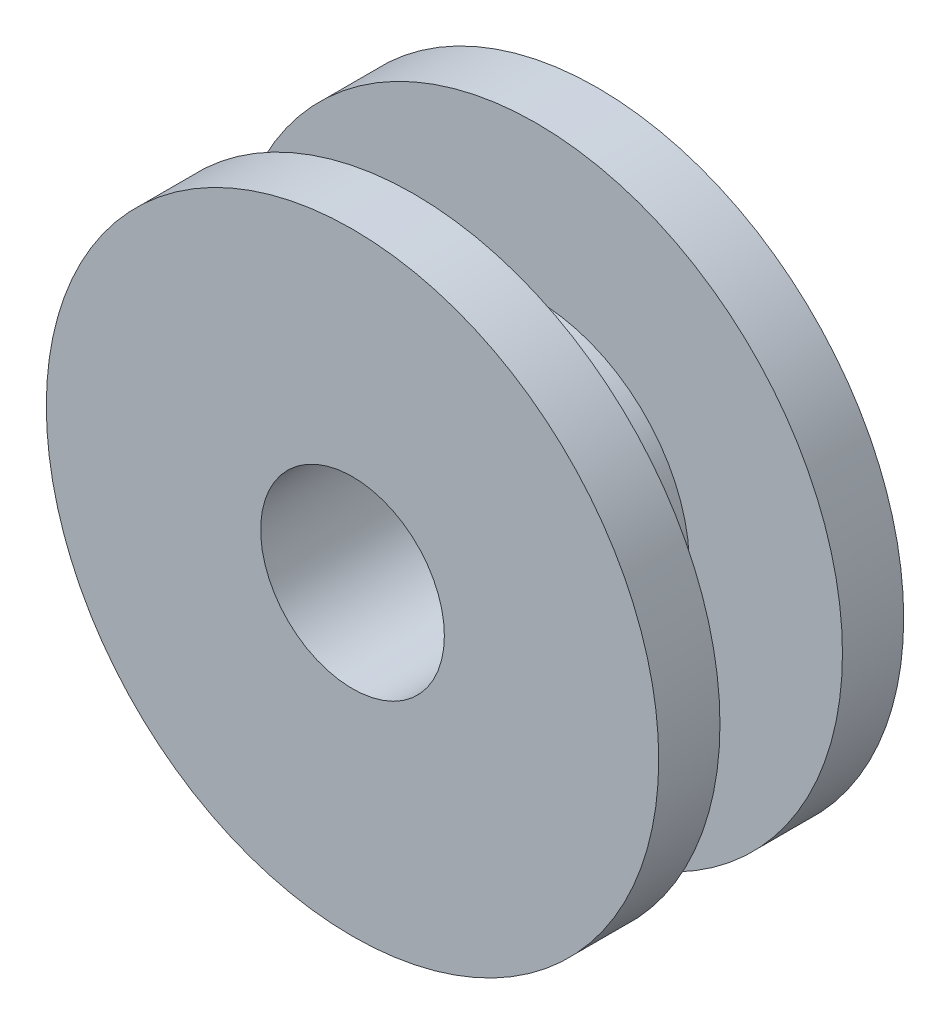
SolidWorks part; units mm, degrees
ref_plane "Front Plane" through (0, 0, 0) normal (0, 0, 1) x (1, 0, 0)
ref_plane "Top Plane" through (0, 0, 0) normal (0, 1, 0) x (1, 0, 0)
ref_plane "Right Plane" through (0, 0, 0) normal (1, 0, 0) x (0, 0, -1)
sketch "Sketch1" plane through (0, 0, 0) normal (0, 0, 1) x (1, 0, 0)
  line L0 (0, 0) -> (0, -2.3) construction
  line L3 (-5, -8) -> (5, -8)
  line L5 (0, -2.3) -> (-3.5, -2.3) construction
  line L6 (-5, 0) -> (-5, -8)
  line L7 (-3.5, -2.3) -> (3.5, -2.3)
  line L8 (-3.5, -2.3) -> (-3.5, -6.3)
  line L9 (-3.5, -6.3) -> (3.5, -6.3)
  line L10 (3.5, -2.3) -> (3.5, -6.3)
  line L11 (5, 0) -> (5, -8)
  circle A1 centre (0, 0) radius 3
  arc A2 (5, 0) -> (-5, 0) centre (0, 0) ccw
  dimension "D1" = 8
  dimension "D4" = 6
  dimension "D5" = 3.5
  dimension "D6" = 7
  dimension "D7" = 4
  dimension "D8" = 2.3
extrude "Boss-Extrude1" add sketch "Sketch1" along normal blind 7 contours L3 A1 L7 L10 L9 L8 region at (-4.836, -4, 0)
sketch "Sketch2" plane through (0, -8, 0) normal (0, -1, 0) x (1, 0, 0)
  circle A0 centre (0, 4) radius 1.35
  dimension "D1" = 2.7
extrude "Cut-Extrude1" cut sketch "Sketch2" against normal up to surface (1.7 mm away) up to face at (0, -6.3, 3.5)
sketch "Sketch3" plane through (0, 0, 0) normal (0, 0, -1) x (-1, 0, 0)
  circle A0 centre (0, 0) radius 10
  dimension "D1" = 20
extrude "Boss-Extrude2" add sketch "Sketch3" along normal blind 2
sketch "Sketch4" plane through (0, 0, -2) normal (0, 0, -1) x (-1, 0, 0)
  circle A0 centre (0, 0) radius 5
  dimension "D1" = 10
extrude "Boss-Extrude3" add sketch "Sketch4" along normal blind 4
sketch "Sketch5" plane through (0, 0, -6) normal (0, 0, -1) x (-1, 0, 0)
  circle A0 centre (0, 0) radius 10
  dimension "D1" = 20
extrude "Boss-Extrude4" add sketch "Sketch5" along normal blind 2
sketch "Sketch6" plane through (0, 0, 0) normal (0, 0, 1) x (1, 0, 0)
  circle A0 centre (0, 0) radius 3
  dimension "D1" = 6
extrude "Cut-Extrude2" cut sketch "Sketch6" against normal through all
sketch "Sketch7" plane through (0, 0, 7) normal (0, 0, 1) x (1, 0, 0)
  circle A0 centre (0, 0) radius 17.6493
extrude "Cut-Extrude3" cut sketch "Sketch7" against normal up to surface (7 mm away) up to face at (-10, 0, 0)
